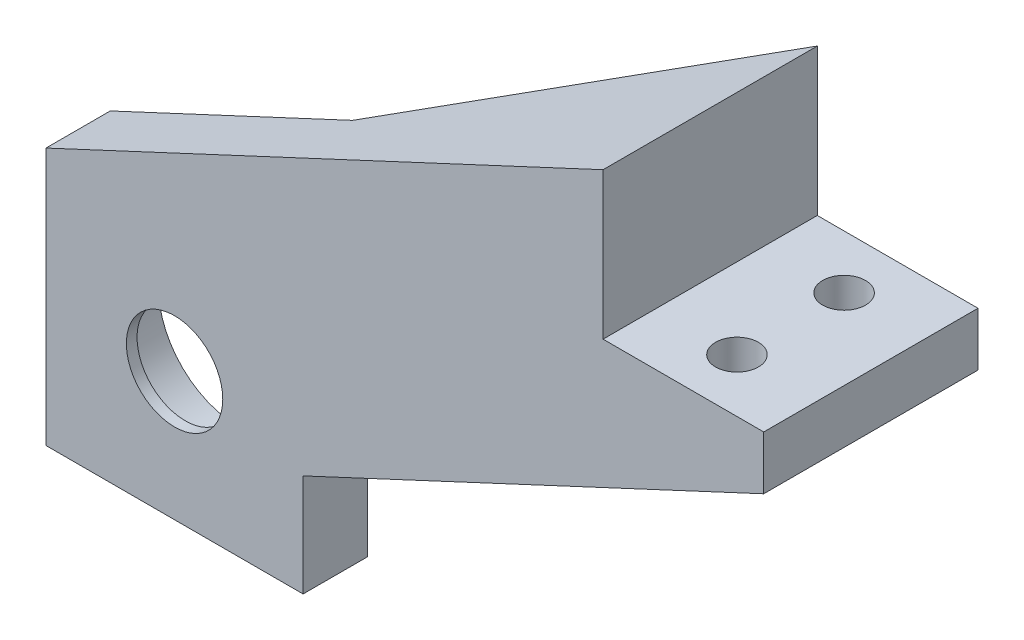
SolidWorks part; units mm, degrees
ref_plane "Front Plane" through (0, 0, 0) normal (0, 0, 1) x (1, 0, 0)
ref_plane "Top Plane" through (0, 0, 0) normal (0, 1, 0) x (1, 0, 0)
ref_plane "Right Plane" through (0, 0, 0) normal (1, 0, 0) x (0, 0, -1)
sketch "Sketch1" plane through (0, 0, 0) normal (0, 0, 1) x (1, 0, 0)
  circle A0 centre (0, 0) radius 7.5
  circle A1 centre (0, 0) radius 4.5
  circle A2 centre (0, 0) radius 10
  dimension "D1" = 15
  dimension "D2" = 20
  dimension "D3" = 9
extrude "Boss-Extrude1" add sketch "Sketch1" against normal up to surface (5 mm away) contours A2 A0 region at (-9.7172, 0, 0)
extrude "Boss-Extrude2" add sketch "Sketch1<3>" along normal blind 1 contours A0 A1 | A2 A0 region at (-7.2879, 0, 0) region at (-9.7172, 0, 0)
sketch "Sketch1<3>" plane through (0, 0, 0) normal (0, 0, 1) x (1, 0, 0) same geometry as "Sketch1"
sketch "Sketch2" plane through (0, 0, 1) normal (0, 0, 1) x (1, 0, 0)
  line L3 (55, 22.6) -> (40, 22.6)
  line L5 (-12, -0.9326) -> (-12, -12)
  line L6 (-12, -12) -> (12, -12)
  line L8 (40, 22.6) -> (40, 17.6)
  line L13 (40, 17.6) -> (55, 17.6)
  line L14 (55, 17.6) -> (55, 22.6)
  line L15 (-86, 22.6) -> (266, 22.6) construction
  line L16 (10.6203, 22.6) -> (-12, 12.052)
  line L17 (-12, -0.9326) -> (-12, 12.052)
  line L18 (40, 22.6) -> (10.6203, 22.6)
  line L19 (55, 17.6) -> (12, -2.4512)
  line L20 (12, -2.4512) -> (12, -12)
  line L21 (10.6203, 22.6) -> (40, 36.3)
  line L23 (34.0705, 37.9485) -> (-8.8692, 17.9254) construction
  line L24 (40, 22.6) -> (40, 34.3) construction
  line L25 (40, 36.3) -> (40, 22.6)
  circle A1 centre (0, 0) radius 10
  circle A2 centre (0, 0) radius 10 construction
  circle M4 centre (0, 0) radius 10
  dimension "D1" = 12
  dimension "D2" = 24
  dimension "D3" = 15
  dimension "D4" = 5
  dimension "D5" = 25
  dimension "D6" = 4
  dimension "D7" = 12
  dimension "D8" = 2
  dimension "D9" = 0
extrude "Boss-Extrude3" add sketch "Sketch2" against normal up to surface (6 mm away) contours L8 M4 | L6 L5 M4 | L8 | L25 L21 L18 region at (47.5, 20.1, 1) region at (16.0369, 9.9628, 1) region at (30.2068, 27.1667, 1) up to face at (-10, 0, -5)
sketch "Sketch3" plane through (0, 22.6, 0) normal (0, -1, 0) x (1, 0, 0)
  line L0 (40, -286) -> (40, 14) construction
  line L1 (55, -5) -> (40, -5)
  line L2 (55, -5) -> (55, -19)
  line L3 (55, -19) -> (40, -19)
  line L4 (40, -5) -> (40, -19)
  line L5 (55, -5) -> (40, -19) construction
  line L6 (55, -19) -> (40, -5) construction
  line L7 (55, 1) -> (12, 1) construction
  line L8 (40, -19) -> (10.6203, -5)
  line L9 (55, -5) -> (55, 1) construction
  line L10 (40, -5) -> (10.6203, -5)
  line L11 (40, -5) -> (-12, -5) construction
  point P4 (47.5, -12)
  dimension "D1" = 20
  dimension "D2" = 29.3797
extrude "Boss-Extrude7" add sketch "Sketch3" along normal up to surface (11.9946 mm away) contours L4 L10 L8 | L1 L4 L3 L2 region at (47.5, 22.6, -12) region at (30.2068, 22.6, -9.6667) up to face at (33.5, 7.5744, -2)
sketch "Sketch4" plane through (0, 22.6, 0) normal (0, -1, 0) x (1, 0, 0)
  line L1 (55, 1) -> (40, 1)
  line L2 (55, 1) -> (55, -19)
  line L3 (55, -19) -> (40, -19)
  line L4 (40, 1) -> (40, -19)
  line L5 (55, 1) -> (40, -19) construction
  line L6 (55, -19) -> (40, 1) construction
  line L7 (55, -19) -> (55, 1) construction
  line L8 (55, -9) -> (40, -9) construction
  line L9 (47.5, -9.9585) -> (44, -11.9793)
  line L10 (44, -11.9793) -> (44, -16.0207)
  line L11 (44, -16.0207) -> (47.5, -18.0415)
  line L12 (47.5, -18.0415) -> (51, -16.0207)
  line L13 (51, -16.0207) -> (51, -11.9793)
  line L14 (51, -11.9793) -> (47.5, -9.9585)
  line L21 (51, -6.0207) -> (47.5, -8.0415)
  line L22 (51, -1.9793) -> (51, -6.0207)
  line L23 (47.5, 0.0415) -> (51, -1.9793)
  line L24 (44, -1.9793) -> (47.5, 0.0415)
  line L25 (44, -6.0207) -> (44, -1.9793)
  line L26 (47.5, -8.0415) -> (44, -6.0207)
  line L27 (55, 1) -> (40, 1) construction
  circle A0 centre (47.5, -14) radius 3.5 construction
  circle A1 centre (47.5, -4) radius 3.5 construction
  circle A2 centre (47.5, -14) radius 2
  circle A3 centre (47.5, -4) radius 2
  point P4 (47.5, -9)
  point P28 (45.75, -10.9689)
  dimension "D3" = 4
  dimension "D1" = 7.5
  dimension "D2" = 7
  dimension "D4" = 5
  dimension "D5" = 15
  dimension "D6" = 20
extrude "Cut-Extrude4" cut sketch "Sketch4" along normal through all contours A2 | A3 region at (47.5, 22.6, -14) region at (47.5, 22.6, -4)
extrude "Cut-Extrude5" cut sketch "Sketch4<3>" along normal through all from offset 3 contours L26 L21 L22 L23 L24 L25 A3 | L13 L14 L9 L10 L11 L12 A2 region at (49.1965, 22.6, -11.0615) region at (49.1965, 22.6, -6.9385)
sketch "Sketch4<3>" plane through (0, 22.6, 0) normal (0, -1, 0) x (1, 0, 0) same geometry as "Sketch4"
extrude "Boss-Extrude8" add sketch "Sketch3<4>" against normal up to surface (13.7 mm away) contours L4 L10 L8 region at (30.2068, 22.6, -9.6667) up to face at (13.3241, 23.8608, -2.6)
sketch "Sketch3<4>" plane through (0, 22.6, 0) normal (0, -1, 0) x (1, 0, 0) same geometry as "Sketch3"
